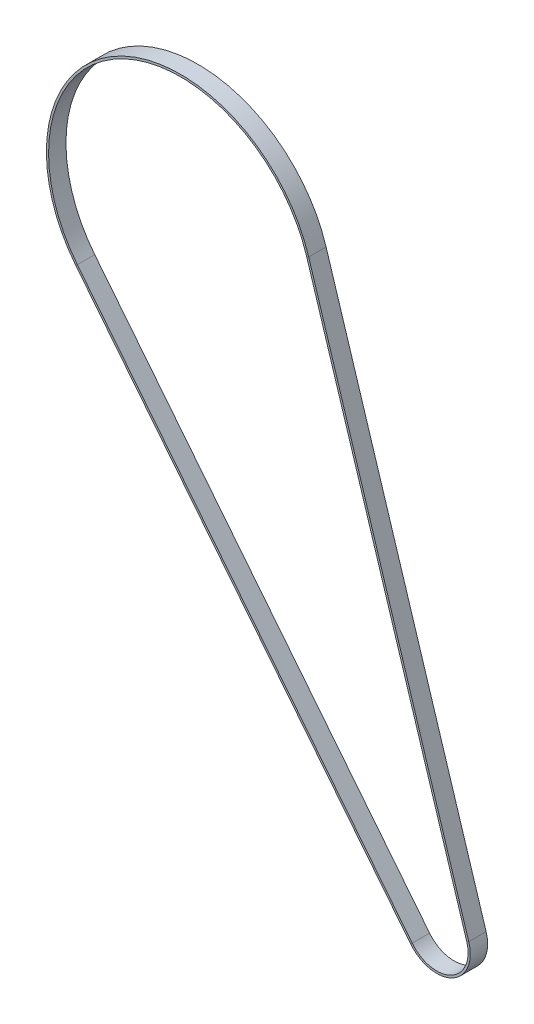
SolidWorks part; units mm, degrees
ref_plane "Front Plane" through (0, 0, 0) normal (0, 0, 1) x (1, 0, 0)
ref_plane "Top Plane" through (0, 0, 0) normal (0, 1, 0) x (1, 0, 0)
ref_plane "Right Plane" through (0, 0, 0) normal (1, 0, 0) x (0, 0, -1)
sketch "Sketch2" plane through (0, 0, 0) normal (0, 0, 1) x (1, 0, 0)
  line L0 (0, 0) -> (1, 0) construction
  line L1 (0, 0) -> (0, 1) construction
  line L2 (30.1607, 80.2223) -> (67.1724, -38.4071)
  line L3 (54.1273, -45.3259) -> (-23.3222, 51.8562)
  arc A0 (-23.3222, 51.8562) -> (30.1607, 80.2223) centre (0.7617, 71.05) cw
  arc A1 (67.1724, -38.4071) -> (54.1273, -45.3259) centre (60.0017, -40.6443) cw
ref_plane "Plane1" through (54.1273, -45.3259, 0) normal (-0.6232, 0.782, 0) x (0.782, 0.6232, 0)
sketch "Sketch3" plane through (54.1273, -45.3259, 0) normal (-0.6232, 0.782, 0) x (0.782, 0.6232, 0)
  line L0 (0, 0) -> (14.5138, 0) construction
  line L1 (-0.2432, 2.0118) -> (0.2568, 2.0118)
  line L2 (-0.2432, 2.0118) -> (-0.2432, -2.0118)
  line L3 (-0.2432, -2.0118) -> (0.2568, -2.0118)
  line L4 (0.2568, 2.0118) -> (0.2568, -2.0118)
  line L5 (0.0068, 2.0118) -> (0.0068, -2.0118) construction
  point P4 (0.2568, 0)
  dimension "D1" = 4.0237
  dimension "D2" = 0.5
sweep "Sweep1" add profiles "Sketch3" path "Sketch2"
